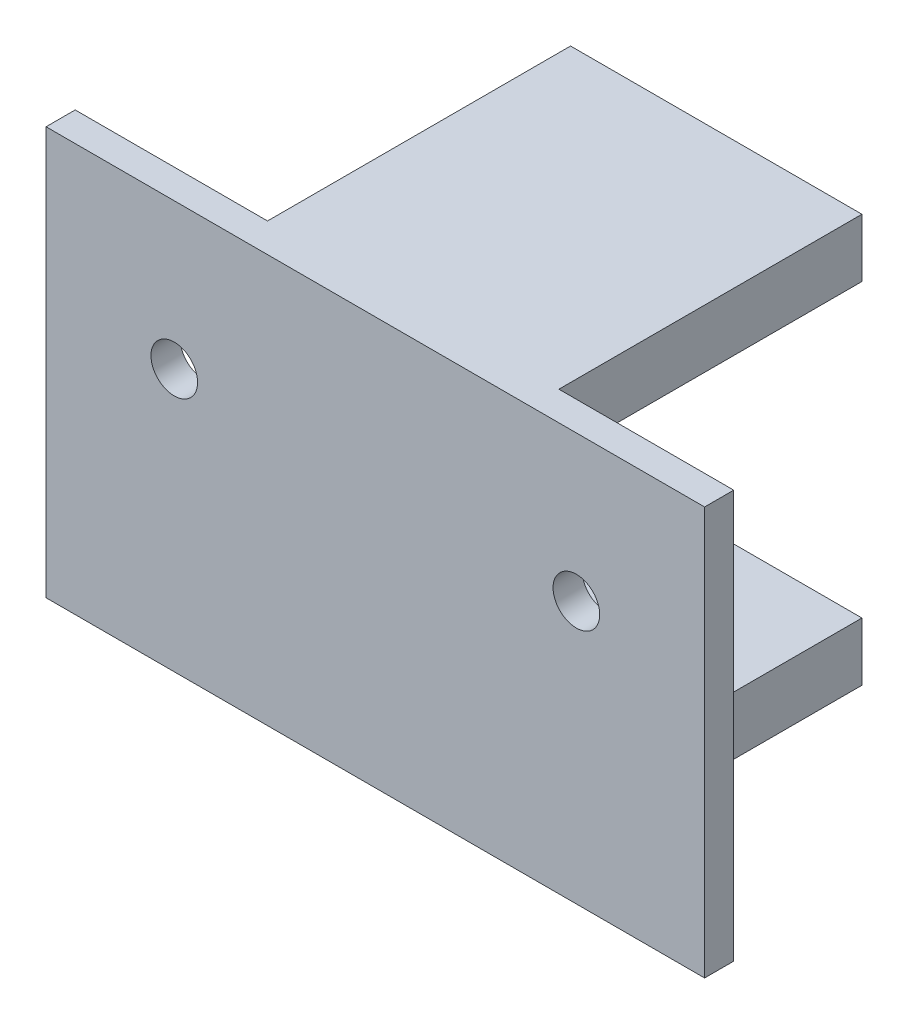
SolidWorks part; units mm, degrees
ref_plane "前视基准面" through (0, 0, 0) normal (0, 0, 1) x (1, 0, 0)
ref_plane "上视基准面" through (0, 0, 0) normal (0, 1, 0) x (1, 0, 0)
ref_plane "右视基准面" through (0, 0, 0) normal (1, 0, 0) x (0, 0, -1)
sketch "草图1" plane through (0, 0, 0) normal (0, 0, 1) x (1, 0, 0)
  line L1 (-56.5, 35) -> (56.5, 35)
  line L2 (-56.5, 35) -> (-56.5, -35)
  line L3 (-56.5, -35) -> (56.5, -35)
  line L4 (56.5, 35) -> (56.5, -35)
  line L5 (-56.5, 35) -> (56.5, -35) construction
  line L6 (-56.5, -35) -> (56.5, 35) construction
  point P0 (0, 0)
  dimension "D1" = 113
  dimension "D2" = 70
extrude "凸台-拉伸1" add sketch "草图1" along normal blind 5 contours L1 L4 L3 L2
sketch "草图2" plane through (0, 0, 0) normal (0, 0, -1) x (-1, 0, 0)
  line L0 (56.5, -35) -> (-56.5, -35) construction
  line L1 (-56.5, 35) -> (-56.5, -35) construction
  line L2 (56.5, 35) -> (-56.5, 35) construction
  line L3 (-26.5, -35) -> (23.5, -35)
  line L4 (-26.5, -35) -> (-26.5, -25)
  line L5 (-26.5, -25) -> (23.5, -25)
  line L6 (23.5, -35) -> (23.5, -25)
  line L7 (-26.5, 35) -> (23.5, 35)
  line L8 (-26.5, 35) -> (-26.5, 25)
  line L9 (-26.5, 25) -> (23.5, 25)
  line L10 (23.5, 35) -> (23.5, 25)
  point P0 (-26.5, -35)
  dimension "D1" = 30
  dimension "D2" = 50
  dimension "D3" = 10
  dimension "D4" = 30
  dimension "D5" = 50
  dimension "D6" = 10
extrude "凸台-拉伸2" add sketch "草图2" along normal blind 52
sketch "草图3" plane through (0, 0, 0) normal (0, 0, -1) x (-1, 0, 0)
  line L0 (-26.5, 35) -> (-56.5, 35) construction
  line L2 (-56.5, 35) -> (-56.5, -35) construction
  line L3 (56.5, 35) -> (23.5, 35) construction
  line L4 (56.5, 35) -> (56.5, -35) construction
  circle A0 centre (-34.5, 10) radius 4
  circle A1 centre (34.5, 10) radius 4
  point P0 (-34.5, 10)
  point P9 (40, 35)
  dimension "D3" = 25
  dimension "D1" = 25
  dimension "D2" = 22
  dimension "D4" = 22
extrude "切除-拉伸1" cut sketch "草图3" against normal through all
sketch "草图5" plane through (0, 0, 5) normal (0, 0, 1) x (1, 0, 0)
  line L0 (-56.5, 35) -> (56.5, 35) construction
  line L1 (-56.5, 35) -> (-56.5, -35) construction
  circle A0 centre (-54.5, 15) radius 2
  circle A1 centre (54.5, 15) radius 2
  circle A2 centre (54.5, -5) radius 2
  circle A3 centre (-54.5, -5) radius 2
  point P0 (-54.5, 15)
  dimension "D1" = 20
  dimension "D2" = 2
  dimension "D3" = 2
  dimension "D4" = 2
